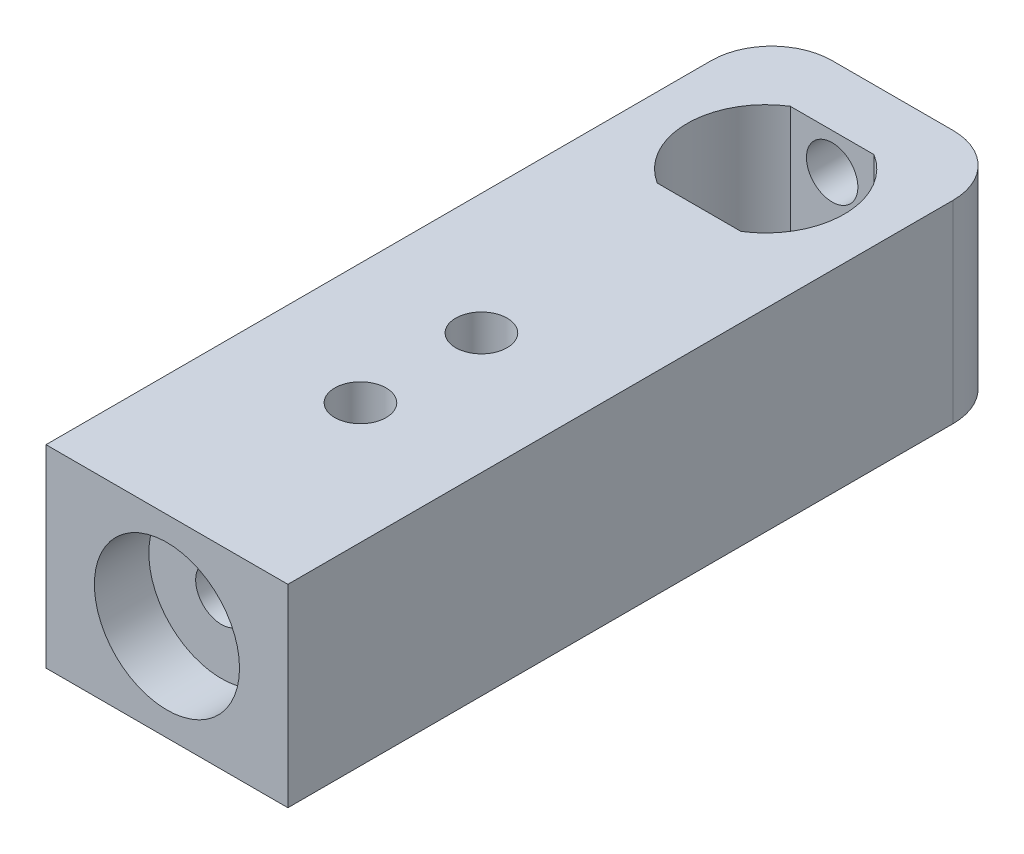
SolidWorks part; units mm, degrees
ref_plane "Alzado" through (0, 0, 0) normal (0, 0, 1) x (1, 0, 0)
ref_plane "Planta" through (0, 0, 0) normal (0, 1, 0) x (1, 0, 0)
ref_plane "Vista lateral" through (0, 0, 0) normal (1, 0, 0) x (0, 0, -1)
sketch "Croquis1" plane through (0, 0, 0) normal (0, 1, 0) x (1, 0, 0)
  line L1 (-10, -30) -> (10, -30)
  line L2 (-10, -30) -> (-10, 30)
  line L3 (-10, 30) -> (10, 30)
  line L4 (10, -30) -> (10, 30)
  line L5 (-10, -30) -> (10, 30) construction
  line L6 (-10, 30) -> (10, -30) construction
  point P0 (0, 0)
  dimension "D1" = 20
  dimension "60" = 60
extrude "Saliente-Extruir1" add sketch "Croquis1" along normal blind 16
sketch "Croquis2" plane through (0, 16, 0) normal (0, 1, 0) x (1, 0, 0)
  line L0 (0, 30) -> (0, 19.5) construction
  line L1 (10, 30) -> (-10, 30) construction
  line L2 (-3.4641, 25) -> (3.4641, 25)
  line L3 (-3.4641, 14) -> (3.4641, 14)
  arc A0 (-3.4641, 25) -> (-3.4641, 14) centre (0, 19.5) ccw
  arc A1 (3.4641, 14) -> (3.4641, 25) centre (0, 19.5) ccw
  dimension "D3" = 13
  dimension "D1" = 5.5
  dimension "D2" = 5.5
  dimension "D4" = 5
extrude "Cortar-Extruir1" cut sketch "Croquis2" against normal through all
sketch "Croquis3" plane through (0, 0, -30) normal (0, 0, -1) x (-1, 0, 0)
  line L0 (0, 0) -> (0, 16) construction
  line L1 (-10, 0) -> (10, 0) construction
  line L2 (-10, 16) -> (10, 16) construction
  circle A0 centre (0, 13) radius 2.125
  circle A1 centre (0, 5) radius 2.125
  dimension "D1" = 4.25
  dimension "D2" = 8
  dimension "D3" = 3
  dimension "D4" = 4.25
extrude "Cortar-Extruir2" cut sketch "Croquis3" against normal up to surface (5 mm away) up to face at (0, 8, -25)
sketch "Croquis4" plane through (0, 16, 0) normal (0, 1, 0) x (1, 0, 0)
  line L0 (0, 14) -> (0, -30) construction
  line L1 (-3.4641, 14) -> (3.4641, 14) construction
  line L2 (-10, -30) -> (10, -30) construction
  line L3 (10, -30) -> (10, 30) construction
  circle A3 centre (0, -4) radius 2.125
  circle A5 centre (0, -14) radius 2.125
  dimension "D1" = 10
  dimension "D3" = 18
  dimension "D4" = 10
  dimension "D2" = 4.25
  dimension "D5" = 10
extrude "Cortar-Extruir3" cut sketch "Croquis4" against normal blind 8
fillet "Redondeo1" radius 5 2 edges at (-10, 8, -30) (10, 8, -30)
sketch "Croquis5" plane through (0, 0, 30) normal (0, 0, 1) x (1, 0, 0)
  line L0 (-10, 0) -> (10, 16) construction
  circle A0 centre (0, 8) radius 6
  dimension "D1" = 12
extrude "Cortar-Extruir4" cut sketch "Croquis5" against normal blind 4.5
sketch "Croquis6" plane through (0, 0, 25.5) normal (0, 0, 1) x (1, 0, 0)
  circle A0 centre (0, 8) radius 2.125
  dimension "D1" = 4.25
extrude "Cortar-Extruir5" cut sketch "Croquis6" against normal blind 8
